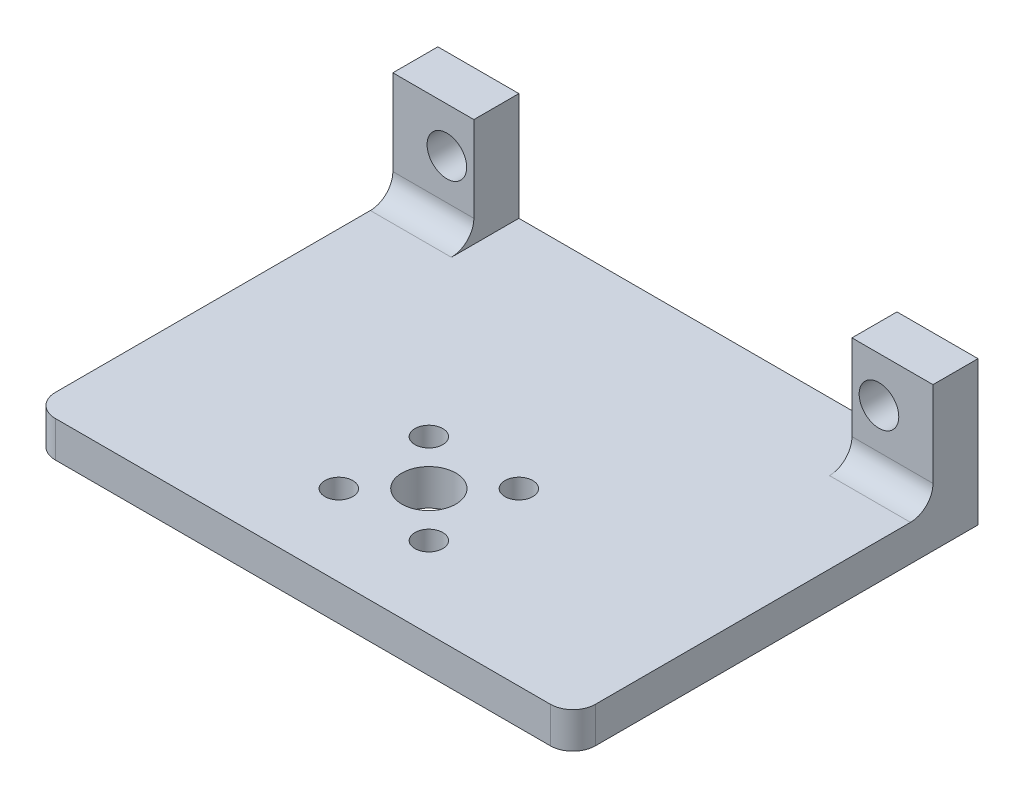
SolidWorks part; units mm, degrees
ref_plane "Front Plane" through (0, 0, 0) normal (0, 0, 1) x (1, 0, 0)
ref_plane "Top Plane" through (0, 0, 0) normal (0, 1, 0) x (1, 0, 0)
ref_plane "Right Plane" through (0, 0, 0) normal (1, 0, 0) x (0, 0, -1)
sketch "Sketch1" plane through (0, 0, 0) normal (0, 0, 1) x (1, 0, 0)
  line L0 (-82.0256, 30) -> (-82.0256, -25.5559) construction
  line L2 (-112.0256, 7.6852) -> (-112.0256, 27.1852)
  line L4 (-103.0256, 7.6852) -> (-103.0256, 27.1852)
  line L9 (-112.0256, 27.1852) -> (-112.0256, 31.6852)
  line L10 (-112.0256, 7.6852) -> (-52.0256, 7.6852)
  line L11 (-112.0256, 7.6852) -> (-112.0256, 3.6852)
  line L12 (-112.0256, 3.6852) -> (-52.0256, 3.6852)
  line L13 (-52.0256, 7.6852) -> (-52.0256, 3.6852)
  line L14 (-112.0256, 31.6852) -> (-103.0256, 31.6852)
  line L15 (-103.0256, 31.6852) -> (-103.0256, 27.1852)
  line L16 (-52.0256, 27.1852) -> (-52.0256, 31.6852)
  line L17 (-112.0256, 31.6852) -> (-52.0256, 31.6852)
  line L18 (-112.0256, 31.6852) -> (-112.0256, 35.6852)
  line L19 (-112.0256, 35.6852) -> (-52.0256, 35.6852)
  line L20 (-52.0256, 31.6852) -> (-52.0256, 35.6852)
  line L21 (-61.0256, 31.6852) -> (-61.0256, 27.1852)
  line L22 (-61.0256, 7.6852) -> (-61.0256, 27.1852)
  line L23 (-52.0256, 7.6852) -> (-52.0256, 27.1852)
  circle A0 centre (-106.0256, 24.6852) radius 2.2
  circle A1 centre (-106.0256, 14.6852) radius 2.2
  circle A2 centre (-58.0256, 14.6852) radius 2.2
  circle A3 centre (-58.0256, 24.6852) radius 2.2
  point P29 (-103.0256, 29.6852)
  point P32 (-112.0256, 29.6852)
  dimension "D3" = 4.4
  dimension "D4" = 4.4
  dimension "D12" = 3
  dimension "D1" = 22
  dimension "D2" = 4
  dimension "D5" = 10
  dimension "D6" = 7
  dimension "D7" = 60
  dimension "D8" = 42
  dimension "D9" = 4
  dimension "D10" = 55.5559
  dimension "D11" = 3
  dimension "D13" = 7
extrude "Boss-Extrude1" add sketch "Sketch1" along normal blind 45 contours L10 L0 L12 L13 | L0 L10 L11 L12 region at (-67.0256, 5.6852, 0) region at (-97.0256, 5.6852, 0)
extrude "Boss-Extrude2" add sketch "Sketch1<3>" along normal blind 5 contours L2 L10 L4 A1 A0 | L10 L23 L16 L17 L21 L22 A2 A3 region at (-107.7714, 19.6852, 0) region at (-56.2799, 19.6852, 0)
sketch "Sketch1<3>" plane through (0, 0, 0) normal (0, 0, 1) x (1, 0, 0) same geometry as "Sketch1"
sketch "Sketch2" plane through (0, 7.6852, 0) normal (0, 1, 0) x (1, 0, 0)
  line L0 (-82.0256, -6.4694) -> (-82.0256, -26.5346) construction
  line L1 (-96.5112, -31) -> (-67.862, -31) construction
  line L2 (-52.0256, -45) -> (-52.0256, -5) construction
  line L3 (-112.0256, -45) -> (-52.0256, -45) construction
  circle A0 centre (-82.0256, -31) radius 3
  circle A1 centre (-77.0256, -26) radius 1.55
  circle A2 centre (-87.0256, -26) radius 1.55
  circle A3 centre (-77.0256, -36) radius 1.55
  circle A4 centre (-87.0256, -36) radius 1.55
  dimension "D1" = 6
  dimension "D2" = 3.1
  dimension "D3" = 3.1
  dimension "D4" = 5
  dimension "D5" = 5
  dimension "D6" = 10
  dimension "D7" = 5
  dimension "D8" = 30
  dimension "D9" = 28.6493
  dimension "D10" = 14
extrude "Cut-Extrude1" cut sketch "Sketch2" against normal through all
extrude "Boss-Extrude3" add sketch "Sketch1<4>" along normal blind 45 contours L17 L20 L19 L18 L14 region at (-82.0256, 33.6852, 0)
sketch "Sketch1<4>" plane through (0, 0, 0) normal (0, 0, 1) x (1, 0, 0) same geometry as "Sketch1"
fillet "Fillet1" radius 2.5 4 edges at (-52.0256, 5.6852, 45) (-112.0256, 5.6852, 45) (-52.0256, 33.6852, 45) (-112.0256, 33.6852, 45)
fillet "Fillet3" radius 2.5 4 edges at (-107.5256, 7.6852, 5) (-56.5256, 7.6852, 5) (-56.5256, 31.6852, 5) (-107.5256, 31.6852, 5)
sketch "Sketch3" plane through (0, 35.6852, 0) normal (0, 1, 0) x (1, 0, 0)
  line L0 (-52.0256, -42.5) -> (-52.0256, 0) construction
  line L3 (-109.5256, -45) -> (-54.5256, -45) construction
  circle A0 centre (-82.0256, -31) radius 4
  dimension "D3" = 8
  dimension "D1" = 30
  dimension "D2" = 14
extrude "Boss-Extrude4" add sketch "Sketch3" along normal blind 12
sketch "Sketch4" plane through (0, 35.6852, 0) normal (0, 1, 0) x (1, 0, 0)
  circle A0 centre (-82.0256, -31) radius 6
  circle A1 centre (-82.0256, -31) radius 4 construction
  dimension "D1" = 2
extrude "Boss-Extrude5" add sketch "Sketch4" along normal blind 5
fillet "Fillet4" radius 1 1 edges at (-82.0256, 40.6852, 35)
sketch "Sketch5" plane through (-112.0256, 0, 0) normal (-1, 0, 0) x (0, 0, 1)
  line L5 (0, 35.6852) -> (0, 3.6852) construction
  line L6 (0, 19.6852) -> (46.6197, 19.6852)
  line L7 (0, 19.6852) -> (0, 49.1177)
  line L8 (0, 49.1177) -> (46.6197, 49.1177)
  line L9 (46.6197, 19.6852) -> (46.6197, 49.1177)
extrude "Cut-Extrude3" cut sketch "Sketch5" against normal through all
